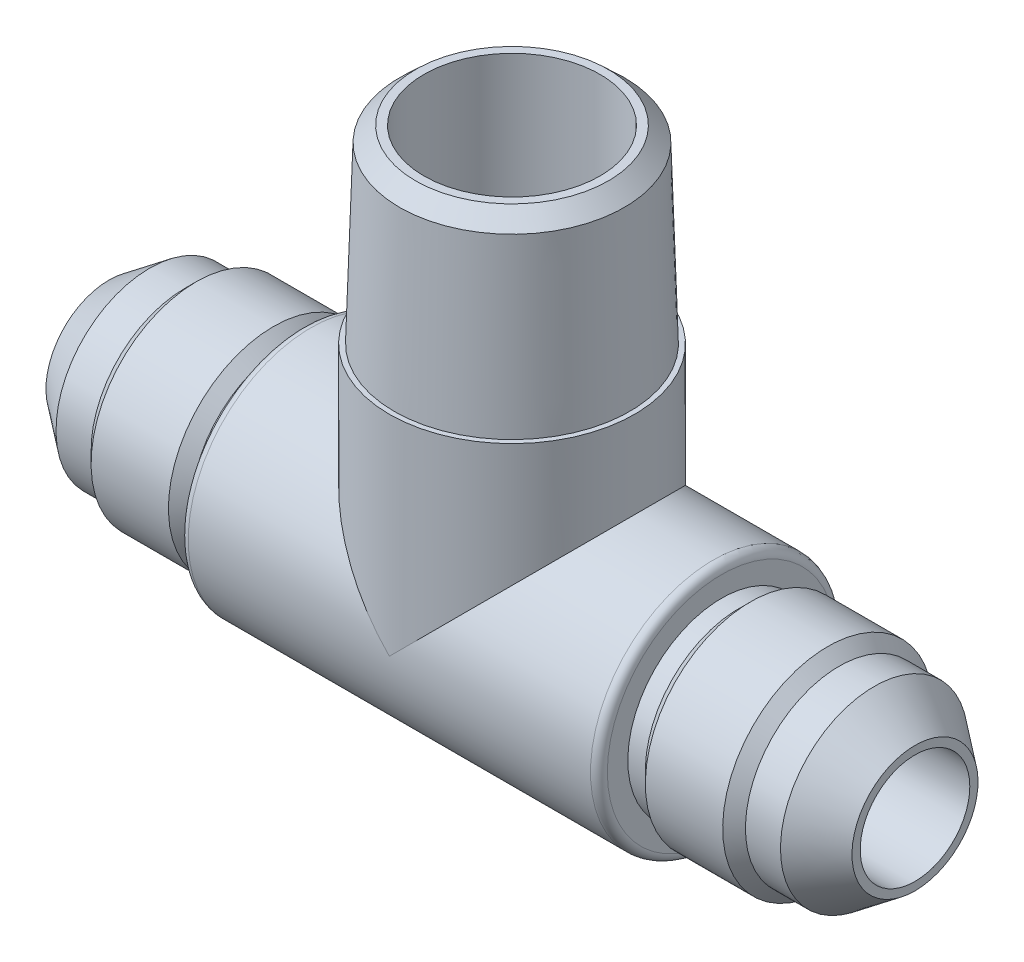
SolidWorks part; units mm, degrees
ref_plane "Front Plane" through (0, 0, 0) normal (0, 0, 1) x (1, 0, 0)
ref_plane "Top Plane" through (0, 0, 0) normal (0, 1, 0) x (1, 0, 0)
ref_plane "Right Plane" through (0, 0, 0) normal (1, 0, 0) x (0, 0, -1)
sketch "Sketch1" plane through (0, 0, 0) normal (0, 0, 1) x (1, 0, 0)
  line L0 (0, 0) -> (-18.9865, 0) construction
  line L1 (0, 0) -> (0, 18.9865) construction
  line L2 (-9.525, 18.9865) -> (9.525, 18.9865) construction
  line L3 (-18.9865, 9.525) -> (-18.9865, -9.525) construction
  line L6 (-36.5125, 9.525) -> (-36.5125, -9.525) construction
  line L8 (-10.668, 36.1163) -> (10.668, 36.1163) construction
  line L9 (0, 0) -> (0, 36.1163) construction
  line L10 (-18.9865, 11.1125) -> (-18.9865, -11.1125) construction
  line L12 (-11.1125, 18.9865) -> (11.1125, 18.9865) construction
  point P15 (0, 22.5603)
  dimension "S" = 17.526
  dimension "Pipe Thread Dia" = 21.336
  dimension "V" = 36.1163
  dimension "TE" = 13.556
  dimension "OA" = 22.225
ref_plane "Plane1" through (-36.5125, 0, 0) normal (1, 0, 0) x (0, 0, -1)
sketch "Sketch2" plane through (-36.5125, 0, 0) normal (1, 0, 0) x (0, 0, -1)
  circle A0 centre (0, 0) radius 9.525
  dimension "Thread OD" = 19.05
extrude "Extrude1" add sketch "Sketch2" along normal up to vertex (17.526 mm away) up to point (-18.9865, 0, 0)
sketch "Sketch3" plane through (-36.5125, 0, 0) normal (-1, 0, 0) x (0, 0, 1)
  circle A0 centre (0, 0) radius 9.525 construction
  circle A1 centre (0, 0) radius 9.525
curve "Helix/Spiral1" pitch 1.5875 height 36.5125 turns 23 parameters "pitch"=1.5875
sketch "Sketch4" plane through (0, 0, 0) normal (0, 0, 1) x (1, 0, 0)
  line L0 (-37.9016, 9.525) -> (-37.3062, 8.4939)
  line L1 (-37.3062, 8.4939) -> (-37.1078, 8.4939)
  line L2 (-37.1078, 8.4939) -> (-36.5125, 9.525)
  line L3 (-37.9016, 9.525) -> (-36.5125, 9.525)
  line L6 (-37.207, 9.525) -> (-37.207, 8.4939) construction
  line L7 (-37.6039, 9.0094) -> (-36.8102, 9.0094) construction
  line L8 (-36.5125, 9.525) -> (-36.5125, -9.525) construction
  dimension "D1" = 0.1984
  dimension "D2" = 0.7937
  dimension "D3" = 60
sweep "Cut-Sweep1" [suppressed] cut profiles "Sketch4" path "Helix/Spiral1"
sketch "Sketch5" plane through (0, 0, 0) normal (0, 0, 1) x (1, 0, 0)
  line L0 (-36.5125, 6.35) -> (-36.5125, -6.35) construction
  line L1 (-32.8189, 8.4939) -> (-29.6439, 8.4939)
  line L2 (-29.6439, 8.4939) -> (-28.6128, 9.525)
  line L3 (-36.5125, 5.7106) -> (-36.5125, -5.7106) construction
  line L4 (-28.6128, 9.525) -> (-36.5125, 9.525)
  line L5 (-37.9016, 9.525) -> (-36.5125, 9.525) construction
  line L6 (-18.9865, 9.525) -> (-18.9865, -9.525) construction
  line L7 (-18.9865, 8.4939) -> (-20.574, 8.4939)
  line L8 (-20.574, 8.4939) -> (-21.6051, 9.525)
  line L9 (-21.6051, 9.525) -> (-18.9865, 9.525)
  line L10 (-18.9865, 8.4939) -> (-18.9865, 9.525)
  line L11 (-27.2626, -9.525) -> (-27.2626, 0) construction
  line L12 (-18.9865, 0) -> (-36.5125, 0) construction
  line L13 (-36.5125, 9.525) -> (-36.5125, -9.525) construction
  line L14 (-36.5125, 5.7106) -> (-32.8189, 8.4939)
  line L15 (-36.5125, 9.525) -> (-36.5125, 5.7106)
  line L16 (0, 0) -> (-18.9865, 0) construction
  point P16 (-27.2626, -9.525)
  dimension "D3" = 45
  dimension "D5" = 45
  dimension "D6" = 1.5875
  dimension "Tube OD" = 12.7
  dimension "D2" = 11.4211
  dimension "D1" = 37
  dimension "D4" = 3.175
  dimension "D7" = 2.3813
revolve "Cut-Revolve1" cut sketch "Sketch5" angle 360 about L0
ref_plane "Plane2" through (-18.9865, 0, 0) normal (1, 0, 0) x (0, 0, -1)
sketch "Sketch15" plane through (-18.9865, 0, 0) normal (1, 0, 0) x (0, 0, -1)
  circle A0 centre (0, 0) radius 11.1125
extrude "Boss-Extrude1" add sketch "Sketch15" along normal up to vertex (18.9865 mm away) up to point (0, 0, 0)
sketch "Sketch16" plane through (0, 0, 0) normal (1, 0, 0) x (0, 0, -1)
  circle A0 centre (0, 0) radius 4.9657
  dimension "Min ID" = 9.9314
extrude "Cut-Extrude1" cut sketch "Sketch16" against normal through all
ref_plane "Plane3" through (0, 18.9865, 0) normal (0, 1, 0) x (-1, 0, 0)
sketch "Sketch20" plane through (0, 18.9865, 0) normal (0, 1, 0) x (-1, 0, 0)
  circle A0 centre (0, 0) radius 11.1125
extrude "Boss-Extrude2" add sketch "Sketch20" against normal up to vertex (18.9865 mm away) separate body up to point (0, 0, 0)
sketch "Sketch22" plane through (0, 18.9865, 0) normal (0, 1, 0) x (-1, 0, 0)
  circle A0 centre (0, 0) radius 10.668
extrude "Boss-Extrude3" add sketch "Sketch22" along normal up to vertex (17.1298 mm away) draft 1.75 separate body up to point (0, 36.1163, 0)
sketch "Sketch23" plane through (0, 36.1163, 0) normal (0, 1, 0) x (1, 0, 0)
  circle A0 centre (0, 0) radius 10.1446 construction
  circle A1 centre (0, 0) radius 10.1446
curve "Helix/Spiral2" parameters "Pitch"=1.8143
chamfer "Chamfer1" distance 1.3607 angle 45 1 edges at (0, 36.1163, 10.1446) first distance on face at (0, 36.1163, 10.1446)
sketch "Sketch25" plane through (0, 18.9865, 0) normal (0, -1, 0) x (1, 0, 0)
  circle A1 centre (0, 0) radius 10.668
  circle A2 centre (0, 0) radius 10.668
  dimension "D1" = 0
sketch "Sketch24" plane through (0, 0, 0) normal (0, 0, 1) x (1, 0, 0)
  line L0 (10.2428, 37.8738) -> (10.2428, 36.0596) construction
  line L1 (10.2428, 36.0596) -> (8.6716, 36.9667) construction
  line L2 (8.6716, 36.9667) -> (10.2428, 37.8738) construction
  line L3 (8.868, 37.0801) -> (8.868, 36.8533)
  line L4 (8.6716, 36.9667) -> (8.868, 36.9667) construction
  line L5 (10.0464, 37.7605) -> (10.0464, 36.173) construction
  line L6 (10.0464, 36.9667) -> (10.2428, 36.9667) construction
  line L7 (10.1446, 36.9667) -> (10.1446, 36.1163) construction
  line L8 (10.1446, 37.8172) -> (10.2428, 36.0596)
  line L9 (10.2428, 36.0596) -> (8.868, 36.8533)
  line L10 (8.868, 37.0801) -> (10.1446, 37.8172)
  dimension "D1" = 1.8143
  dimension "D2" = 0.2268
sweep "Cut-Sweep2" [suppressed] cut profiles "Sketch24" path "Helix/Spiral2"
extrude "Boss-Extrude4" add sketch "Sketch25" against normal up to vertex (17.1298 mm away) draft 15 up to point (10.668, 36.1163, 0)
sketch "Sketch28" plane through (0, 36.1163, 0) normal (0, 1, 0) x (1, 0, 0)
  circle A2 centre (0, 0) radius 7.9784
  circle A3 centre (0, 0) radius 7.9784
  dimension "D1" = 0.762
extrude "Cut-Extrude6" cut sketch "Sketch28" against normal up to vertex (17.1298 mm away) up to point (0, 18.9865, 0)
fillet "Fillet1" radius 0.762 1 edges at (-18.9865, 0, -11.1125)
sketch "Sketch10" plane through (0, 0, 0) normal (1, 0, 0) x (0, 0, -1)
  line L0 (0, 0) -> (-12.651, 0) construction
ref_axis "Axis1" through (0, 0, 12.651) along (0, 0, -1)
pattern_circular "CirPattern1" count 2 over 180 about axis through (0, 0, 12.651) along (0, 0, -1) reverse direction yes of bodies 110 103
combine bodies "Combine2" operation type add bodies to combine 110 122 114 105
sketch "Sketch30" plane through (0, 0, 0) normal (0, 0, 1) x (1, 0, 0)
  line L0 (0, 18.9865) -> (0, 9.4932)
  line L1 (0, 18.9865) -> (-10.922, 18.9865)
  line L2 (0, 0) -> (0, 18.9865) construction
  line L3 (-10.922, 18.9865) -> (0, 9.4932) construction
  line L4 (-5.461, 14.2399) -> (-6.1275, 13.4731) construction
  line L5 (-10.922, 18.9865) -> (-10.922, 18.4785)
  arc A0 (-10.922, 18.4785) -> (0, 9.4932) centre (13.649, 37.215) ccw
  point P2 (0, 9.4932)
  dimension "D1" = 0.254
  dimension "D2" = 1.016
  dimension "D3" = 0.508
revolve "Revolve1" add sketch "Sketch30" angle 360 about L0
sketch "Sketch26" plane through (-36.5125, 0, 0) normal (-1, 0, 0) x (0, 0, 1)
  circle A0 centre (0, 0) radius 4.9657 construction
  circle A1 centre (0, 0) radius 4.9657
extrude "Cut-Extrude4" cut sketch "Sketch26" against normal through all
sketch "Sketch29" plane through (0, 0, 0) normal (0, 1, 0) x (1, 0, 0)
  circle A0 centre (0, 0) radius 4.9657
  dimension "D1" = 9.9314
extrude "Cut-Extrude7" cut sketch "Sketch29" along normal through all
sketch "Sketch12" plane through (0, 0, 0) normal (0, 0, 1) x (1, 0, 0)
  line L0 (0, 0) -> (0, 36.1163) construction
  line L2 (0, 0) -> (-36.5125, 0) construction
  line L3 (7.9784, 36.1163) -> (-7.9784, 36.1163) construction
sketch "Sketch13" plane through (0, 0, 0) normal (1, 0, 0) x (0, 0, -1)
  line L0 (9.525, 18.9865) -> (-9.525, 18.9865)
  line L1 (0, 0) -> (0, 18.9865) construction
  line L3 (9.525, 0) -> (-9.525, 0)
  circle A0 centre (0, 0) radius 4.9657
  circle A1 centre (0, 0) radius 4.9657 construction
  dimension "D1" = 19.05
sketch "Sketch31" [suppressed] plane through (-36.5125, 0, 0) normal (-1, 0, 0) x (0, 0, 1)
  point P0 (0, 0)
  point P1 (0, 0)
sketch "Sketch32" [suppressed] plane through (36.5125, 0, 0) normal (1, 0, 0) x (0, 0, -1)
  point P0 (0, 0)
other "CPoint1" parameters "Diameter"=12.7, "StubLength"=6.35
ref_axis "Axis2" through (-46.5125, 0, 0) along (1, 0, 0)
other "CPoint2" parameters "Diameter"=12.7, "StubLength"=19.05
ref_axis "Axis3" through (46.5125, 0, 0) along (-1, 0, 0)
equation "\"D1@Sketch1\" = \"Thread OD@Sketch2\""
equation "\"D3@Helix/Spiral1\" = \"Q@Sketch1\""
equation "\"D1@Sketch4\" = \"pitch@Helix/Spiral1\"*.125"
equation "\"D2@Sketch4\" = \"pitch@Helix/Spiral1\"*.5"
equation "\"D6@Sketch5\" = \"pitch@Helix/Spiral1\"*1"
equation "\"D4@Sketch5\" = \"pitch@Helix/Spiral1\"*2"
equation "\"D1@Sketch13\" = \"D1@Sketch1\""
equation "\"D7@Sketch5\" = \"pitch@Helix/Spiral1\"*1.5"
equation "\"D2@Sketch5\" = \"Min ID@Sketch16\"*1.15"
equation "\"D1@Sketch24\" = \"Pitch@Helix/Spiral2\""
equation "\"D2@Sketch24\" = \"Pitch@Helix/Spiral2\"/8"
equation "\"D1@Chamfer1\" = \"Pitch@Helix/Spiral2\"*.750"
equation "\"D1@Sketch29\" =  \"Min ID@Sketch16\""
